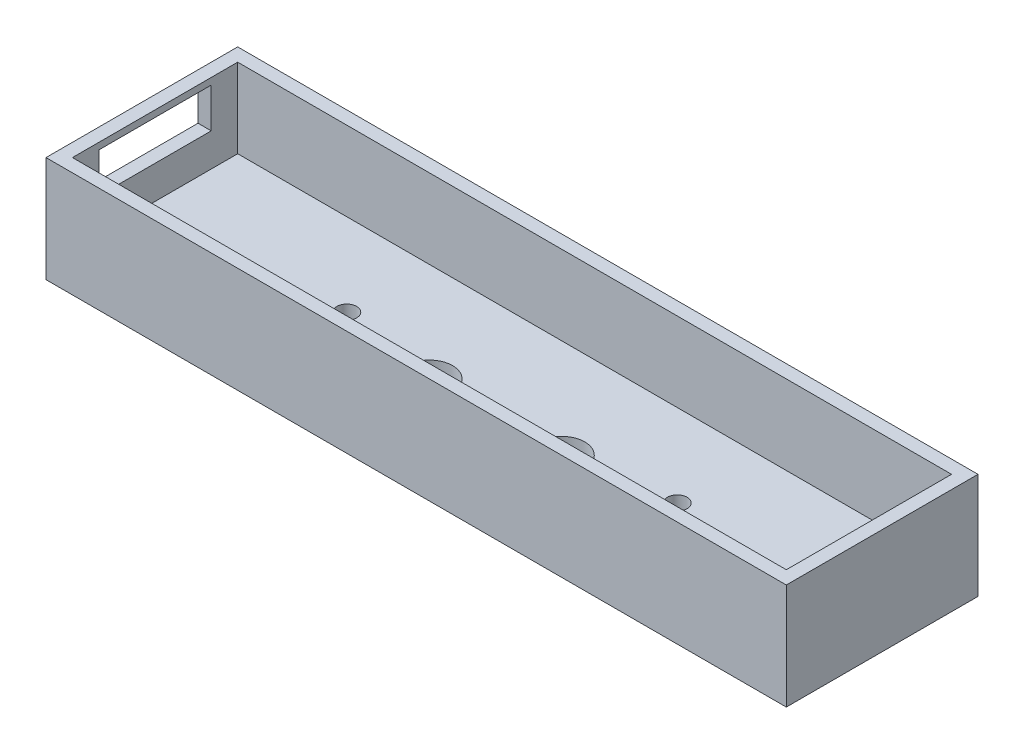
SolidWorks part; units mm, degrees
ref_plane "Front Plane" through (0, 0, 0) normal (0, 0, 1) x (1, 0, 0)
ref_plane "Top Plane" through (0, 0, 0) normal (0, 1, 0) x (1, 0, 0)
ref_plane "Right Plane" through (0, 0, 0) normal (1, 0, 0) x (0, 0, -1)
sketch "Sketch1" plane through (0, 0, 0) normal (0, 1, 0) x (1, 0, 0)
  line L1 (-42.4555, 18.7875) -> (65.5445, 18.7875)
  line L2 (-42.4555, 18.7875) -> (-42.4555, -6.2125)
  line L3 (-42.4555, -6.2125) -> (65.5445, -6.2125)
  line L4 (65.5445, 18.7875) -> (65.5445, -6.2125)
  dimension "D1" = 108
  dimension "D2" = 25
extrude "Boss-Extrude1" add sketch "Sketch1" along normal blind 4
sketch "Sketch2" plane through (0, 4, 0) normal (0, 1, 0) x (1, 0, 0)
  line L0 (-42.4555, 18.7875) -> (-42.4555, -6.2125) construction
  line L1 (65.5445, 18.7875) -> (-42.4555, 18.7875) construction
  circle A0 centre (-13.4555, 6.2875) radius 1.5
  circle A1 centre (36.5445, 6.2875) radius 1.5
  point P8 (0, 0)
  dimension "D1" = 3
  dimension "D2" = 3
  dimension "D3" = 50
  dimension "D4" = 29
  dimension "D5" = 12.5
  dimension "D6" = 12.5
extrude "Cut-Extrude1" cut sketch "Sketch2" against normal up to next
sketch "Sketch3" plane through (0, 0, 0) normal (0, -1, 0) x (-1, 0, 0)
  circle A0 centre (-36.5445, 6.2875) radius 3.5
  circle A1 centre (13.4555, 6.2875) radius 3.5
  circle A2 centre (-36.5445, 6.2875) radius 1.5 construction
  circle A3 centre (13.4555, 6.2875) radius 1.5 construction
  point P4 (0, 0)
  circle M3 centre (13.4555, 6.2875) radius 1.5
  dimension "D1" = 7
  dimension "D2" = 7
extrude "Cut-Extrude3" cut sketch "Sketch3" against normal blind 2 contours A1 M3 | A0 region at (-10.0545, 0, -6.2875)
sketch "Sketch4" plane through (0, 4, 0) normal (0, 1, 0) x (1, 0, 0)
  line L0 (65.5445, -6.2125) -> (65.5445, 18.7875) construction
  line L1 (-42.4555, -6.2125) -> (65.5445, -6.2125) construction
  circle A0 centre (21.5445, 3.7875) radius 1.25
  circle A1 centre (1.5445, 3.7875) radius 1.25
  dimension "D1" = 2.5
  dimension "D2" = 2.5
  dimension "D3" = 20
  dimension "D4" = 44
  dimension "D5" = 10
  dimension "D6" = 10
extrude "Cut-Extrude4" cut sketch "Sketch4" against normal up to next
sketch "Sketch5" plane through (0, 4, 0) normal (0, 1, 0) x (1, 0, 0)
  circle A0 centre (21.5445, 3.7875) radius 3.5
  circle A1 centre (1.5445, 3.7875) radius 3.5
  circle A2 centre (21.5445, 3.7875) radius 1.25 construction
  circle A3 centre (1.5445, 3.7875) radius 1.25 construction
  dimension "D1" = 7
  dimension "D2" = 7
extrude "Cut-Extrude5" cut sketch "Sketch5" against normal blind 1.7
sketch "Sketch6" plane through (0, 4, 0) normal (0, 1, 0) x (1, 0, 0)
  line L0 (-42.4555, -6.2125) -> (65.5445, -6.2125) construction
  line L1 (67.5445, 18.7875) -> (65.5445, 18.7875)
  line L2 (67.5445, 18.7875) -> (67.5445, -6.2125)
  line L3 (67.5445, -6.2125) -> (65.5445, -6.2125)
  line L4 (65.5445, 18.7875) -> (65.5445, -6.2125)
  line L5 (67.5445, -6.2125) -> (-44.4555, -6.2125)
  line L6 (67.5445, -6.2125) -> (67.5445, -8.2125)
  line L7 (67.5445, -8.2125) -> (-44.4555, -8.2125)
  line L8 (-44.4555, -6.2125) -> (-44.4555, -8.2125)
  line L9 (-44.4555, -6.2125) -> (-42.4555, -6.2125)
  line L10 (-44.4555, -6.2125) -> (-44.4555, 18.7875)
  line L11 (-44.4555, 18.7875) -> (-42.4555, 18.7875)
  line L12 (-42.4555, -6.2125) -> (-42.4555, 18.7875)
  line L13 (67.5445, 20.7875) -> (-44.4555, 20.7875)
  line L14 (67.5445, 20.7875) -> (67.5445, 18.7875)
  line L15 (67.5445, 18.7875) -> (-44.4555, 18.7875)
  line L16 (-44.4555, 20.7875) -> (-44.4555, 18.7875)
  line L17 (65.5445, -6.2125) -> (65.5445, 18.7875) construction
  line L18 (65.5445, 18.7875) -> (-42.4555, 18.7875) construction
  line L19 (-42.4555, 18.7875) -> (-42.4555, -6.2125) construction
  line M20 (-42.4555, 18.7875) -> (-42.4555, -6.2125)
  line M21 (-42.4555, -6.2125) -> (65.5445, -6.2125)
  line M23 (65.5445, 18.7875) -> (-42.4555, 18.7875)
  dimension "D1" = 2
  dimension "D2" = 2
  dimension "D3" = 2
  dimension "D4" = 2
  dimension "D5" = 2
  dimension "D6" = 0
  dimension "D7" = 0
  dimension "D8" = 0
  dimension "D9" = 0
  dimension "D10" = 2
  dimension "D11" = 0
  dimension "D12" = 0
  dimension "D13" = 2
  dimension "D14" = 0
  dimension "D15" = 2
  dimension "D16" = 0
extrude "Boss-Extrude2" add sketch "Sketch6" along normal blind 12 and the other way blind 4 contours L13 L16 L11 L1 L14 M23 | L5 L8 L7 L6 L3 M21 | L11 L10 L5 M20 | L2 L1 L4 L3 region at (11.5445, 4, -19.7875) region at (11.5445, 4, 7.2125) region at (-43.4555, 4, -6.2875)
sketch "Sketch8" plane through (-44.4555, 0, 0) normal (-1, 0, 0) x (0, 0, 1)
  line L0 (-14.7875, 9) -> (2.2125, 9)
  line L1 (-14.7875, 9) -> (-14.7875, 15)
  line L2 (-14.7875, 15) -> (2.2125, 15)
  line L3 (2.2125, 9) -> (2.2125, 15)
  line L4 (-20.7875, 16) -> (8.2125, 16) construction
  line L5 (-20.7875, 0) -> (-20.7875, 16) construction
  dimension "D1" = 17
  dimension "D2" = 6
  dimension "D3" = 1
  dimension "D4" = 6
extrude "Cut-Extrude7" cut sketch "Sketch8" against normal up to next
